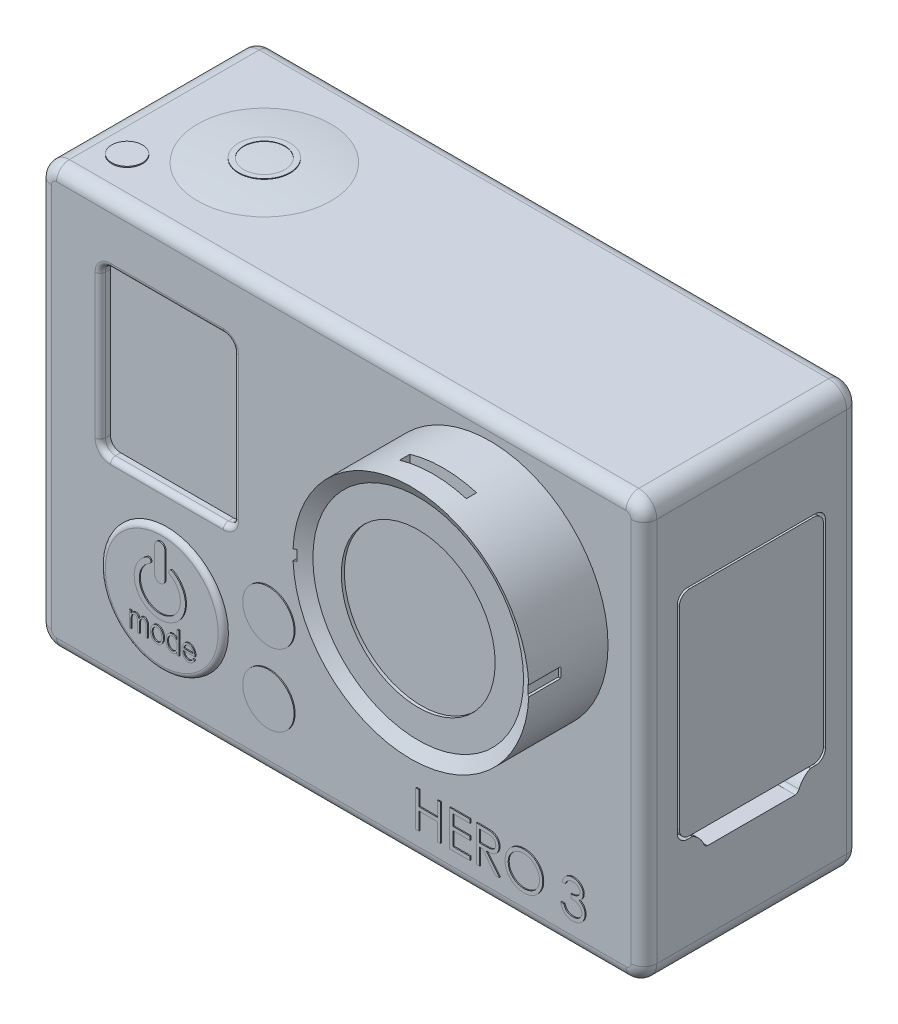
SolidWorks part; units mm, degrees
ref_plane "Front Plane" through (0, 0, 0) normal (0, 0, 1) x (1, 0, 0)
ref_plane "Top Plane" through (0, 0, 0) normal (0, 1, 0) x (1, 0, 0)
ref_plane "Right Plane" through (0, 0, 0) normal (1, 0, 0) x (0, 0, -1)
sketch "Sketch1" plane through (0, 0, 0) normal (0, 0, 1) x (1, 0, 0)
  line L1 (27.75, -20.5) -> (-27.75, -20.5)
  line L2 (29.5, -18.75) -> (29.5, 18.75)
  line L3 (27.75, 20.5) -> (-27.75, 20.5)
  line L4 (-29.5, -18.75) -> (-29.5, 18.75)
  line L5 (29.5, -20.5) -> (-29.5, 20.5) construction
  line L6 (29.5, 20.5) -> (-29.5, -20.5) construction
  arc A0 (29.5, 18.75) -> (27.75, 20.5) centre (27.75, 18.75) ccw
  arc A1 (27.75, -20.5) -> (29.5, -18.75) centre (27.75, -18.75) ccw
  arc A2 (-27.75, -20.5) -> (-29.5, -18.75) centre (-27.75, -18.75) cw
  arc A3 (-27.75, 20.5) -> (-29.5, 18.75) centre (-27.75, 18.75) ccw
  point P0 (0, 0)
  dimension "D3" = 1.75
  dimension "D1" = 59
  dimension "D2" = 41
extrude "Boss-Extrude1" add sketch "Sketch1" along normal blind 21
sketch "Sketch3" plane through (0, 0, 21) normal (0, 0, 1) x (1, 0, 0)
  line L0 (27.75, 20.5) -> (-27.75, 20.5) construction
  line L1 (-22.5, 14.5) -> (-11.5, 14.5)
  line L2 (-23.5, 13.5) -> (-23.5, -0.5)
  line L3 (-22.5, -1.5) -> (-11.5, -1.5)
  line L4 (-10.5, 13.5) -> (-10.5, -0.5)
  line L5 (-29.5, 18.75) -> (-29.5, -18.75) construction
  arc A0 (-23.5, -0.5) -> (-22.5, -1.5) centre (-22.5, -0.5) ccw
  arc A1 (-11.5, -1.5) -> (-10.5, -0.5) centre (-11.5, -0.5) ccw
  arc A2 (-11.5, 14.5) -> (-10.5, 13.5) centre (-11.5, 13.5) cw
  arc A3 (-22.5, 14.5) -> (-23.5, 13.5) centre (-22.5, 13.5) ccw
  point P12 (-10.5, -1.5)
  point P15 (-10.5, 14.5)
  point P18 (-23.5, 14.5)
  dimension "D5" = 1
  dimension "D1" = 13
  dimension "D2" = 16
  dimension "D3" = 6
  dimension "D4" = 6
extrude "Cut-Extrude1" cut sketch "Sketch3" against normal blind 1
sketch "Sketch4" plane through (0, 0, 21) normal (0, 0, 1) x (1, 0, 0)
  line L0 (-27.75, -20.5) -> (27.75, -20.5) construction
  line L1 (-23.5, 20.5) -> (-23.5, -20.5) construction
  line L3 (27.75, 20.5) -> (-27.75, 20.5) construction
  line L4 (-23.5, 13.5) -> (-23.5, -0.5) construction
  circle A0 centre (-17, -10.5) radius 6
  dimension "D1" = 12
  dimension "D2" = 10
  dimension "D3" = 6.5
extrude "Boss-Extrude2" add sketch "Sketch4" along normal blind 0.5
fillet "Fillet1" radius 0.5 1 edges at (-11, -10.5, 21.5)
sketch "Sketch7" plane through (0, 0, 21) normal (0, 0, 1) x (1, 0, 0)
  line L0 (27.75, 20.5) -> (-27.75, 20.5) construction
  line L1 (29.5, -18.75) -> (29.5, 18.75) construction
  circle A0 centre (14.5, 7) radius 11.5
  point P2 (26, 7)
  point P3 (14.5, 18.5)
  dimension "D1" = 23
  dimension "D2" = 2
  dimension "D3" = 3.5
extrude "Boss-Extrude9" add sketch "Sketch7" along normal blind 8
sketch "Sketch8" plane through (0, 0, 29) normal (0, 0, 1) x (1, 0, 0)
  circle A1 centre (14.5, 7) radius 9
  dimension "D1" = 18
extrude "Cut-Extrude3" cut sketch "Sketch8" against normal blind 1
chamfer "Chamfer1" distance 3 angle 30 1 edges at (23.5, 7, 29)
sketch "Sketch9" plane through (0, 0, 21) normal (0, 0, 1) x (1, 0, 0)
  text T0 "HERO 3"
extrude "Boss-Extrude10" add sketch "Sketch9" along normal blind 0.1
sketch "Sketch10" plane through (0, 0, 21) normal (0, 0, 1) x (1, 0, 0)
  line L0 (-27.75, -20.5) -> (27.75, -20.5) construction
  circle A0 centre (-7, -7) radius 2.5
  circle A1 centre (-7, -14) radius 2.5
  circle A2 centre (-17, -10.5) radius 6 construction
  dimension "D1" = 5
  dimension "D2" = 5
  dimension "D3" = 6.5
  dimension "D4" = 7
  dimension "D5" = 10
extrude "Boss-Extrude11" add sketch "Sketch10" along normal blind 0.1
sketch "Sketch11" plane through (0, 0, 28) normal (0, 0, 1) x (1, 0, 0)
  circle A0 centre (14.5, 7) radius 7.5
  dimension "D1" = 15
extrude "Cut-Extrude4" cut sketch "Sketch11" against normal blind 0.3
sketch "Sketch12" plane through (0, 20.5, 0) normal (0, 1, 0) x (1, 0, 0)
  line L0 (27.75, -21) -> (-27.75, -21) construction
  line L2 (-27.75, -21) -> (-27.75, 0) construction
  circle A0 centre (-16.25, -10.5) radius 6.5
  point P2 (-9.75, -10.5)
  point P3 (-16.25, -4)
  point P4 (-22.75, -10.5)
  point P5 (-16.25, -17)
  dimension "D1" = 13
  dimension "D2" = 4
  dimension "D3" = 5
extrude "Boss-Extrude12" [suppressed] add sketch "Sketch12" along normal blind 0.3
sketch "Sketch14" plane through (0, 0, 21.5) normal (0, 0, 1) x (1, 0, 0)
  line L0 (-17.583, -8.5) -> (-17.583, -6)
  line L2 (-16.583, -6) -> (-16.583, -8.5)
  arc A0 (-17.583, -6) -> (-16.583, -6) centre (-17.083, -6) cw
  arc A1 (-17.583, -8.5) -> (-16.583, -8.5) centre (-17.083, -8.5) ccw
  arc A2 (-18.083, -7.8253) -> (-16.083, -7.8253) centre (-17.083, -9.5574) ccw
  arc A3 (-18.333, -7.3923) -> (-15.833, -7.3923) centre (-17.083, -9.5574) ccw
  arc A4 (-18.333, -7.3923) -> (-18.083, -7.8253) centre (-18.208, -7.6088) cw
  arc A5 (-16.083, -7.8253) -> (-15.833, -7.3923) centre (-15.958, -7.6088) cw
  circle A6 centre (-17, -10.5) radius 5.5 construction
  point P14 (-17.083, -12.0574)
  dimension "D7" = 2
  dimension "D2" = 0.5
  dimension "D10" = 4.5
  dimension "D1" = 2.5
  dimension "D4" = 0.5
  dimension "D5" = 0.5
  dimension "D6" = 1
  dimension "D8" = 1.0574
  dimension "D9" = 0.5
  dimension "D3" = 0.5
extrude "Boss-Extrude14" add sketch "Sketch14" along normal blind 0.1
sketch "Sketch15" plane through (0, 0, 21.5) normal (0, 0, 1) x (1, 0, 0)
  circle A0 centre (-17, -10.5) radius 5.5 construction
  text T0 "mode" font "Century Gothic" height in points 8
  dimension "D1" = 3.75
  dimension "D2" = 3.25
extrude "Boss-Extrude15" add sketch "Sketch15" along normal blind 0.1
fillet "Fillet2" radius 1.25 16 edges at (28.9874, 19.9874, 21) (29.5, 0, 21) (28.9874, -19.9874, 21) (0, -20.5, 21) (-28.9874, -19.9874, 21) (-29.5, 0, 21) (-28.9874, 19.9874, 21) (0, 20.5, 21) (28.9874, 19.9874, 0) (29.5, 0, 0) (28.9874, -19.9874, 0) (0, -20.5, 0) (-28.9874, -19.9874, 0) (-29.5, 0, 0) (-28.9874, 19.9874, 0) (0, 20.5, 0)
sketch "Sketch17" plane through (0, -20.5, 0) normal (0, -1, 0) x (1, 0, 0)
  line L0 (-27.75, 1.25) -> (27.75, 1.25) construction
  line L1 (27.75, 19.75) -> (27.75, 1.25) construction
  circle A0 centre (24.75, 2.75) radius 1
  dimension "D1" = 2
  dimension "D2" = 1.5
  dimension "D3" = 3
extrude "Boss-Extrude17" add sketch "Sketch17" along normal blind 0.1
sketch "Sketch18" plane through (-29.5, 0, 0) normal (-1, 0, 0) x (0, 0, 1)
  line L0 (19.75, -18.75) -> (19.75, 18.75) construction
  line L1 (19.75, -18.75) -> (1.25, -18.75) construction
  circle A0 centre (10.75, -9.75) radius 3
  dimension "D1" = 6
  dimension "D2" = 9
  dimension "D3" = 9
extrude "Boss-Extrude18" add sketch "Sketch18" along normal blind 0.1
sketch "Sketch19" plane through (-29.6, 0, 0) normal (-1, 0, 0) x (0, 0, 1)
  line L0 (12.5178, -9.2322) -> (10.75, -11) construction
  line L1 (19.75, -18.75) -> (1.25, -18.75) construction
  line L3 (10.3964, -10.6464) -> (10.0429, -10.2929) construction
  line L4 (9.9015, -10.1515) -> (9.5479, -9.7979) construction
  line L5 (9.4065, -9.6565) -> (9.0529, -9.3029) construction
  line L6 (7.75, -9.75) -> (13.75, -9.75) construction
  line L7 (13.75, -9.75) -> (10.75, -11) construction
  line L8 (10.75, -11) -> (7.75, -9.75) construction
  circle A0 centre (10.75, -11) radius 0.5
  arc A1 (12.4471, -9.3029) -> (9.0529, -9.3029) centre (10.75, -11) ccw
  arc A2 (9.9015, -10.1515) -> (11.5985, -10.1515) centre (10.75, -11) cw
  arc A3 (9.4065, -9.6565) -> (12.0935, -9.6565) centre (10.75, -11) cw
  arc A4 (10.0429, -10.2929) -> (11.4571, -10.2929) centre (10.75, -11) cw
  arc A5 (9.9015, -10.1515) -> (10.0429, -10.2929) centre (9.9722, -10.2222) ccw
  arc A6 (11.5985, -10.1515) -> (11.4571, -10.2929) centre (11.5278, -10.2222) cw
  arc A7 (9.5479, -9.7979) -> (11.9521, -9.7979) centre (10.75, -11) cw
  arc A8 (12.5885, -9.1615) -> (8.9115, -9.1615) centre (10.75, -11) ccw
  arc A9 (12.0935, -9.6565) -> (11.9521, -9.7979) centre (12.0228, -9.7272) cw
  arc A10 (9.4065, -9.6565) -> (9.5479, -9.7979) centre (9.4772, -9.7272) ccw
  arc A11 (9.0529, -9.3029) -> (8.9115, -9.1615) centre (8.9822, -9.2322) cw
  arc A12 (12.5885, -9.1615) -> (12.4471, -9.3029) centre (12.5178, -9.2322) cw
  circle A13 centre (10.75, -9.75) radius 3 construction
  dimension "D1" = 1
  dimension "D5" = 90
  dimension "D6" = 0.5
  dimension "D7" = 45
  dimension "D2" = 0.2
  dimension "D3" = 0.2
  dimension "D4" = 0.2
extrude "Cut-Extrude5" cut sketch "Sketch19" against normal blind 0.1
sketch "Sketch20" plane through (-29.5, 0, 0) normal (-1, 0, 0) x (0, 0, 1)
  line L0 (1.25, -16.8226) -> (4.25, -16.8226)
  line L1 (1.25, 18.75) -> (1.25, -18.75) construction
  line L2 (4.25, -16.8226) -> (4.25, 17.2763)
  line L3 (4.25, 17.2763) -> (1.25, 17.2763)
  line L4 (1.25, 17.2763) -> (-9.4336, 17.2763)
  line L5 (-9.4336, 17.2763) -> (-9.4336, -16.8226)
  line L6 (-9.4336, -16.8226) -> (1.25, -16.8226)
  dimension "D1" = 3
extrude "Cut-Extrude6" cut sketch "Sketch20" against normal blind 3.5
sketch "Sketch21" plane through (0, 0, 0) normal (0, 0, -1) x (-1, 0, 0)
  line L0 (26, 17.2763) -> (26, -16.8226) construction
  line L1 (23, 18.25) -> (-7, 18.25)
  line L2 (23, 18.25) -> (23, -18.25)
  line L3 (23, -18.25) -> (-7, -18.25)
  line L4 (-7, 18.25) -> (-7, -18.25)
  line L5 (27.75, 19.25) -> (-27.75, 19.25) construction
  line L6 (-27.75, -19.25) -> (27.75, -19.25) construction
  line L7 (22.5, 17.75) -> (-6.5, 17.75)
  line L8 (-6.5, 17.75) -> (-6.5, -17.75)
  line L9 (22.5, -17.75) -> (-6.5, -17.75)
  line L10 (22.5, 17.75) -> (22.5, -17.75)
  dimension "D1" = 30
  dimension "D2" = 3
  dimension "D3" = 1
  dimension "D4" = 1
  dimension "D5" = 0.5
extrude "Cut-Extrude7" cut sketch "Sketch21" against normal blind 2
sketch "Sketch22" plane through (0, 0, 0) normal (0, 0, -1) x (-1, 0, 0)
  text T0 "GoPro" font "Century Gothic" height in points 9
extrude "Cut-Extrude8" cut sketch "Sketch22" against normal blind 0.1
sketch "Sketch23" plane through (0, 0, 0) normal (0, 0, -1) x (-1, 0, 0)
  line L0 (-7, 18.25) -> (-7, -18.25) construction
  line L1 (-16, 7.75) -> (-10, 7.75)
  line L2 (-16, 7.75) -> (-16, -5.25)
  line L3 (-16, -5.25) -> (-10, -5.25)
  line L4 (-10, 7.75) -> (-10, -5.25)
  line L5 (-27.75, -19.25) -> (27.75, -19.25) construction
  dimension "D1" = 6
  dimension "D2" = 13
  dimension "D3" = 3
  dimension "D4" = 14
extrude "Cut-Extrude9" cut sketch "Sketch23" against normal blind 2
sketch "Sketch24" plane through (0, 0, 2) normal (0, 0, -1) x (-1, 0, 0)
  line L0 (-10, 7.75) -> (-16, 7.75) construction
  line L1 (-14.4, 7.25) -> (-10.5, 7.25)
  line L2 (-14.4, 7.25) -> (-14.4, -4.75)
  line L3 (-14.4, -4.75) -> (-10.5, -4.75)
  line L4 (-10.5, 7.25) -> (-10.5, -4.75)
  line L5 (-10, -5.25) -> (-10, 7.75) construction
  line L6 (-16, -5.25) -> (-10, -5.25) construction
  dimension "D1" = 0.5
  dimension "D2" = 0.5
  dimension "D3" = 0.5
  dimension "D4" = 4.4
extrude "Boss-Extrude19" add sketch "Sketch24" along normal blind 2
sketch "Sketch25" plane through (0, 0, 0) normal (0, 0, -1) x (-1, 0, 0)
  line L0 (-10.5, 7.25) -> (-14.4, 7.25) construction
  line L1 (-13.4, 7.05) -> (-11.5, 7.05)
  line L2 (-13.4, 7.05) -> (-13.4, -4.55)
  line L3 (-13.4, -4.55) -> (-11.5, -4.55)
  line L4 (-11.5, 7.05) -> (-11.5, -4.55)
  line L5 (-10.5, -4.75) -> (-10.5, 7.25) construction
  line L6 (-14.4, -4.75) -> (-10.5, -4.75) construction
  line L7 (-14.4, 7.25) -> (-14.4, -4.75) construction
  dimension "D1" = 0.2
  dimension "D2" = 1
  dimension "D3" = 0.2
  dimension "D4" = 1
extrude "Cut-Extrude10" cut sketch "Sketch25" against normal blind 1
chamfer "Chamfer2" distance 1 angle 40 1 edges at (11.5, 1.25, 0)
sketch "Sketch26" plane through (0, 0, 0) normal (0, 0, -1) x (-1, 0, 0)
  line L0 (27.75, 19.25) -> (-27.75, 19.25) construction
  line L1 (-26.25, 9.25) -> (-23.25, 9.25)
  line L2 (-26.25, 9.25) -> (-26.25, -9.25)
  line L3 (-26.25, -9.25) -> (-23.25, -9.25)
  line L4 (-23.25, 9.25) -> (-23.25, -9.25)
  line L5 (-27.75, -19.25) -> (27.75, -19.25) construction
  line L6 (-28.25, 18.75) -> (-28.25, -18.75) construction
  dimension "D1" = 3
  dimension "D2" = 10
  dimension "D3" = 10
  dimension "D4" = 2
extrude "Cut-Extrude11" cut sketch "Sketch26" against normal blind 3
sketch "Sketch27" plane through (0, 0, 0) normal (0, 0, -1) x (-1, 0, 0)
  line L0 (-23.25, 9.25) -> (-26.25, 9.25) construction
  line L3 (-26.25, 9.25) -> (-26.25, -9.25) construction
  circle A0 centre (-24.75, 12.25) radius 1.5
  point P2 (-24.75, 9.25)
  dimension "D1" = 3
  dimension "D2" = 3
extrude "Boss-Extrude20" add sketch "Sketch27" along normal blind 0.1
sketch "Sketch28" plane through (29.5, 0, 0) normal (1, 0, 0) x (0, 0, -1)
  line L0 (-19.75, 18.75) -> (-19.75, -18.75) construction
  line L1 (-16.75, -9.75) -> (-4.3, -9.75)
  line L2 (-17.75, -8.75) -> (-17.75, 10.5)
  line L3 (-16.75, 11.5) -> (-4.3, 11.5)
  line L4 (-3.3, -8.75) -> (-3.3, 10.5)
  line L6 (-19.75, -18.75) -> (-1.25, -18.75) construction
  line L7 (-16.55, 11.3) -> (-4.5, 11.3)
  line L8 (-3.5, -8.55) -> (-3.5, 10.3)
  line L9 (-16.55, -9.55) -> (-4.5, -9.55)
  line L10 (-17.55, -8.55) -> (-17.55, 10.3)
  line L11 (-17.75, -9.75) -> (-17.75, 11.5) construction
  line L12 (-17.75, 11.5) -> (-3.3, 11.5) construction
  line L13 (-17.55, 11.3) -> (-3.5, 11.3) construction
  line L14 (-17.55, -9.55) -> (-17.55, 11.3) construction
  line L15 (-3.3, -9.75) -> (-3.3, 11.5) construction
  line L16 (-3.5, -9.55) -> (-3.5, 11.3) construction
  line L17 (-17.75, -9.75) -> (-3.3, -9.75) construction
  line L18 (-17.55, -9.55) -> (-3.5, -9.55) construction
  arc A0 (-17.75, 10.5) -> (-16.75, 11.5) centre (-16.75, 10.5) cw
  arc A1 (-16.55, 11.3) -> (-17.55, 10.3) centre (-16.55, 10.3) ccw
  arc A2 (-4.3, 11.5) -> (-3.3, 10.5) centre (-4.3, 10.5) cw
  arc A3 (-4.5, 11.3) -> (-3.5, 10.3) centre (-4.5, 10.3) cw
  arc A4 (-4.3, -9.75) -> (-3.3, -8.75) centre (-4.3, -8.75) ccw
  arc A5 (-3.5, -8.55) -> (-4.5, -9.55) centre (-4.5, -8.55) cw
  arc A6 (-16.75, -9.75) -> (-17.75, -8.75) centre (-16.75, -8.75) cw
  arc A7 (-16.55, -9.55) -> (-17.55, -8.55) centre (-16.55, -8.55) cw
  point P15 (-17.75, 11.5)
  dimension "D6" = 1
  dimension "D2" = 2
  dimension "D4" = 9
  dimension "D5" = 0.2
extrude "Cut-Extrude12" cut sketch "Sketch28" against normal blind 2
sketch "Sketch29" plane through (29.5, 0, 0) normal (1, 0, 0) x (0, 0, -1)
  line L0 (-14.8079, -11.2603) -> (-6.2421, -11.2603)
  line L1 (-10.525, 11.3) -> (-10.525, -29.2471) construction
  line L2 (-4.5, 11.3) -> (-16.55, 11.3) construction
  line L3 (-16.75, -9.75) -> (-4.3, -9.75) construction
  line L4 (-16.2716, -9.75) -> (-4.7784, -9.75)
  arc A0 (-16.2716, -9.75) -> (-15.16, -10.964) centre (-17.3462, -11.8499) cw
  arc A1 (-15.16, -10.964) -> (-14.8079, -11.2603) centre (-14.7035, -10.779) ccw
  arc A2 (-5.89, -10.964) -> (-6.2421, -11.2603) centre (-6.3465, -10.779) cw
  arc A3 (-4.7784, -9.75) -> (-5.89, -10.964) centre (-3.7038, -11.8499) ccw
  point P14 (-10.525, -11.2603)
  point P15 (-10.525, -11.2603)
  point P18 (-10.525, -11.2603)
extrude "Cut-Extrude13" cut sketch "Sketch29" against normal blind 2
sketch "Sketch30" plane through (-29.5, 0, 0) normal (-1, 0, 0) x (0, 0, 1)
  line L0 (14, -18.75) -> (14, 18.75) construction
  line L1 (14.6, 12.5) -> (14.6, 10.29)
  line L2 (13.4, 10.29) -> (13.4, 12.5)
  line L3 (13.35, 10.29) -> (13.35, 12.5)
  line L4 (14.65, 12.5) -> (14.65, 10.29)
  line L5 (19.75, 18.75) -> (1.25, 18.75) construction
  line L6 (19.75, -18.75) -> (1.25, -18.75) construction
  line L8 (19.75, 20.5) -> (1.25, 20.5) construction
  line L9 (21, 18.75) -> (21, -18.75) construction
  circle A0 centre (14, 10.29) radius 0.5
  circle A1 centre (14, 11.39) radius 0.5
  circle A2 centre (14, 12.5) radius 0.5
  arc A3 (13.4, 10.29) -> (14.6, 10.29) centre (14, 10.29) ccw
  arc A4 (14.6, 12.5) -> (13.4, 12.5) centre (14, 12.5) ccw
  arc A5 (14.65, 12.5) -> (13.35, 12.5) centre (14, 12.5) ccw
  arc A6 (13.35, 10.29) -> (14.65, 10.29) centre (14, 10.29) ccw
  dimension "D1" = 1
  dimension "D2" = 1
  dimension "D3" = 1
  dimension "D4" = 1.1
  dimension "D8" = 0.1
  dimension "D6" = 0.6
  dimension "D10" = 0.1
  dimension "D5" = 1.11
  dimension "D7" = 0.6
  dimension "D11" = 7
  dimension "D12" = 8
  dimension "D9" = 0.05
extrude "Cut-Extrude15" cut sketch "Sketch30" against normal blind 0.2 contours A6 L0 A3 L2 A4 A5 L3 | L0 A6 L4 A5 A4 L1 A3 | L0 A1 | L0 A2 | A2 L0 | A1 L0 | L0 A0 | A0 L0
chamfer "Chamfer3" distance 0.2 angle 40 2 edges at (11.95, -4.55, 0) (11.95, 7.05, 0)
sketch "Sketch32" plane through (-26, 0, 0) normal (-1, 0, 0) x (0, 0, 1)
  line L1 (1.25, 17.2763) -> (0, 17.2763)
  line L2 (1.25, 17.2763) -> (1.25, -16.8226)
  line L3 (1.25, -16.8226) -> (0, -16.8226)
  line L4 (0, 17.2763) -> (0, -16.8226)
extrude "Boss-Extrude21" add sketch "Sketch32" along normal blind 1
sketch "Sketch33" plane through (0, 20.5, 0) normal (0, 1, 0) x (1, 0, 0)
  line L1 (11.25, -25.5613) -> (17.75, -25.5613)
  line L2 (11.25, -25.5613) -> (11.25, -26.5613)
  line L3 (11.25, -26.5613) -> (17.75, -26.5613)
  line L4 (17.75, -25.5613) -> (17.75, -26.5613)
  line L5 (26, -28.7113) -> (3, -28.7113) construction
  line L6 (3, -28.7113) -> (26, -28.7113) construction
  point P9 (14.5, -26.5613)
  point P10 (14.5, -28.7113)
  dimension "D1" = 6.5
  dimension "D2" = 1
  dimension "D4" = 2.15
extrude "Cut-Extrude17" cut sketch "Sketch33" against normal blind 3.5
sketch "Sketch34" plane through (0, -20.5, 0) normal (0, -1, 0) x (1, 0, 0)
  line L1 (11.25, 26.5613) -> (17.75, 26.5613)
  line L2 (11.25, 26.5613) -> (11.25, 25.5613)
  line L3 (11.25, 25.5613) -> (17.75, 25.5613)
  line L4 (17.75, 26.5613) -> (17.75, 25.5613)
  line L6 (3, 28.7113) -> (26, 28.7113) construction
  line L7 (26, 28.7113) -> (3, 28.7113) construction
  point P6 (14.5, 25.5613)
  point P7 (14.5, 28.7113)
  dimension "D1" = 1
  dimension "D2" = 6.5
  dimension "D3" = 2.15
extrude "Cut-Extrude18" cut sketch "Sketch34" against normal blind 17.5
ref_plane "Plane1" through (0, 0, 25.6) normal (0, 0, 1) x (1, 0, 0)
sketch "Sketch35" plane through (0, 0, 25.6) normal (0, 0, 1) x (1, 0, 0)
  line L0 (26, 7.5) -> (26, 6.5)
  line L1 (3.25, 7.5) -> (3, 7.5)
  line L2 (14.5, 7) -> (14.5, 23.7265) construction
  line L3 (3.25, 7.5) -> (3.25, 6.5)
  line L4 (3.25, 6.5) -> (3, 6.5)
  line L5 (3, 7.5) -> (3, 6.5)
  line L6 (25.75, 6.5) -> (26, 6.5)
  line L7 (25.75, 7.5) -> (25.75, 6.5)
  line L8 (25.75, 7.5) -> (26, 7.5)
  circle A1 centre (14.5, 7) radius 11.5 construction
  dimension "D1" = 11.5
  dimension "D2" = 0.5
  dimension "D3" = 1
  dimension "D4" = 0.25
extrude "Cut-Extrude19" cut sketch "Sketch35" along normal blind 21
ref_plane "Plane2" through (0, 0, 10.5) normal (0, 0, 1) x (1, 0, 0)
sketch "Sketch36" plane through (0, 0, 10.5) normal (0, 0, 1) x (1, 0, 0)
  line L0 (-18, 20.5) -> (-11.5, 20.5)
  line L1 (-27.75, 20.5) -> (27.75, 20.5) construction
  line L2 (-18, 20.5) -> (-18, 20.9)
  line L3 (-18, 20.9) -> (-13.3073, 20.9) construction
  arc A0 (-18, 20.9) -> (-11.5, 20.5) centre (-18, -32.1125) cw
  dimension "D1" = 18
  dimension "D2" = 0.4
  dimension "D3" = 6.5
revolve "Revolve1" add sketch "Sketch36" angle 360 about L2
sketch "Sketch16" plane through (0, 20.5, 0) normal (0, 1, 0) x (1, 0, 0)
  line L1 (-27.75, -19.75) -> (27.75, -19.75) construction
  circle A0 centre (-25.3244, -16.55) radius 1.5
  circle A1 centre (-18, -10.5) radius 6.5 construction
  point P2 (-23.8253, -16.499)
  point P3 (-22.5979, -15.0945)
  dimension "D1" = 3
  dimension "D3" = 3.2
  dimension "D2" = 9.5
extrude "Boss-Extrude16" add sketch "Sketch16" along normal blind 0.1
sketch "Sketch13" plane through (0, 20.5, 0) normal (0, 1, 0) x (1, 0, 0)
  circle A0 centre (-18, -10.5) radius 2.5
  circle A1 centre (-18, -10.5) radius 2
  circle A2 centre (-18, -10.5) radius 6.5 construction
  dimension "D1" = 5
  dimension "D2" = 0.5
extrude "Boss-Extrude13" add sketch "Sketch13" along normal blind 0.4
fillet "Fillet3" radius 0.05 1 edges at (-27, 0.2269, 1.25)
fillet "Fillet4" radius 0.2 7 edges at (-29.1339, -16.8226, 0.3661) (-29.1339, 17.2763, 0.3661) (-29.5, -16.8226, 2.75) (-29.5, 0.2269, 4.25) (-29.5, 17.2763, 2.75) (-27.625, -16.8226, 0) (-27.625, 17.2763, 0)
fillet "Fillet5" radius 0.05 1 edges at (-27, 0.2269, 0)
chamfer "Chamfer4" distance 2 angle 30 1 edges at (-26, 0.2269, 4.25)
fillet "Fillet6" radius 0.5 8 edges at (-23.2071, -1.2071, 21) (-23.5, 6.5, 21) (-23.2071, 14.2071, 21) (-17, 14.5, 21) (-10.7929, 14.2071, 21) (-10.5, 6.5, 21) (-10.7929, -1.2071, 21) (-17, -1.5, 21)
